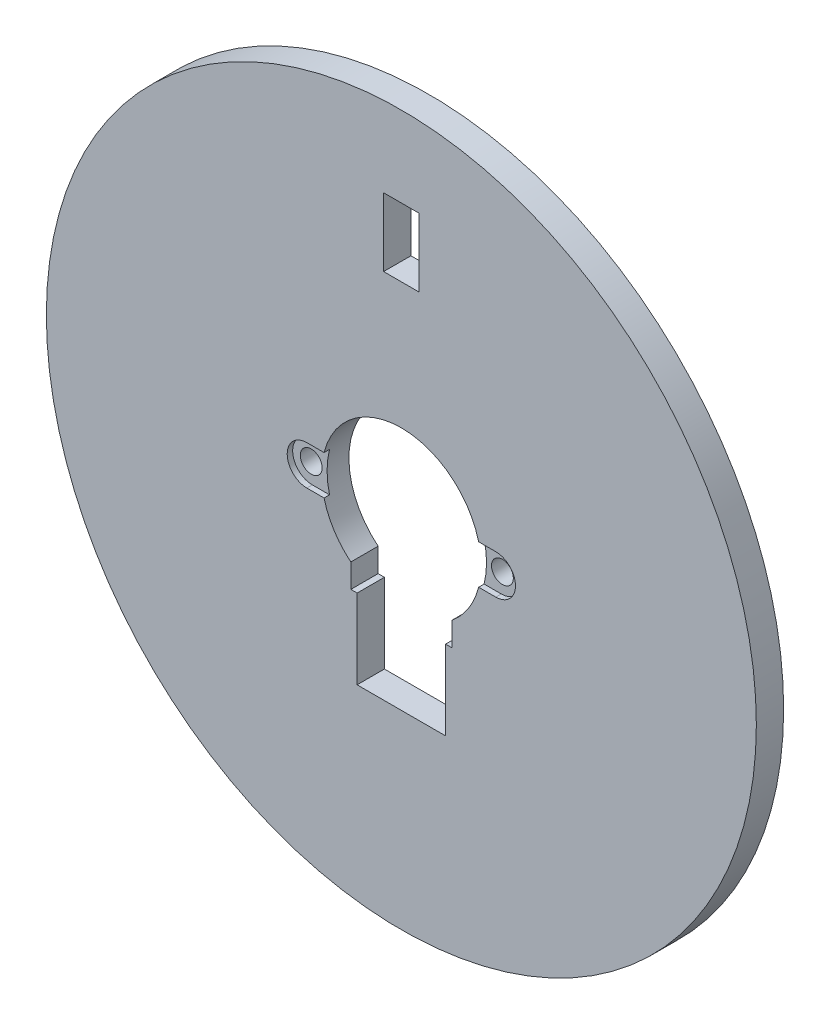
SolidWorks part; units mm, degrees
ref_plane "Front Plane" through (0, 0, 0) normal (0, 0, 1) x (1, 0, 0)
ref_plane "Top Plane" through (0, 0, 0) normal (0, 1, 0) x (1, 0, 0)
ref_plane "Right Plane" through (0, 0, 0) normal (1, 0, 0) x (0, 0, -1)
sketch "Sketch1" plane through (0, 0, 0) normal (0, 0, 1) x (1, 0, 0)
  line L0 (-121.4648, 0) -> (89.658, 0) construction
  line L1 (0, 59.7877) -> (0, -65.1952) construction
  line L2 (-14.1492, 3.6) -> (-17.3, 3.6)
  line L3 (-14.1492, -3.6) -> (-17.3, -3.6)
  line L4 (-9.25, -11.2959) -> (-9.25, -15.647)
  line L5 (14.1492, 3.6) -> (17.3, 3.6)
  line L14 (8.1, -15.647) -> (8.1, -30.2)
  line L15 (14.1492, -3.6) -> (17.3, -3.6)
  line L16 (-8.1, -30.2) -> (8.1, -30.2)
  line L24 (9.25, -11.2959) -> (9.25, -15.647)
  line L25 (8.1, -15.647) -> (9.25, -15.647)
  line L26 (-8.1, -15.647) -> (-9.25, -15.647)
  line L27 (-8.1, -15.647) -> (-8.1, -30.2)
  line L28 (-3.25, 44) -> (3.25, 44) construction
  line L29 (-3.25, 50.25) -> (3.25, 50.25)
  line L30 (-3.25, 50.25) -> (-3.25, 37.75)
  line L31 (-3.25, 37.75) -> (3.25, 37.75)
  line L32 (3.25, 50.25) -> (3.25, 37.75)
  circle A0 centre (0, 0) radius 65
  arc A2 (9.25, -11.2959) -> (-9.25, -11.2959) centre (0, 0) ccw
  arc A3 (17.3, -3.6) -> (17.3, 3.6) centre (17.3, 0) ccw
  arc A4 (-17.3, -3.6) -> (-17.3, 3.6) centre (-17.3, 0) cw
  circle A6 centre (17.5, 0) radius 2
  circle A7 centre (-17.5, 0) radius 2
  circle A8 centre (0, 56) radius 2
  circle A9 centre (0, 32) radius 2
  point P35 (0, -30.2)
  dimension "D2" = 18.5
  dimension "D3" = 14.6
  dimension "D4" = 7.2
  dimension "D8" = 4
  dimension "D5" = 130
  dimension "D13" = 4
  dimension "D6" = 1.15
  dimension "D7" = 0.2
  dimension "D9" = 6.5
  dimension "D10" = 4.3511
  dimension "D11" = 12.5
  dimension "D12" = 44
  dimension "D14" = 30.2
  dimension "D15" = 12
  dimension "D16" = 17.5
extrude "Boss-Extrude1" add sketch "Sketch1" along normal blind 5 contours A0 L3 A4 L2 A2 L5 A3 L15 L24 L25 L14 L16 L27 L26 L4 region at (-63.1615, 0, 0)
extrude "Boss-Extrude2" add sketch "Sketch1<3>" along normal blind 4 contours A4 L3 A2 L2 A7 | L15 A3 L5 A2 A6 region at (-14.6987, 0, 0) region at (15.7246, 3.5013, 0)
sketch "Sketch1<3>" plane through (0, 0, 0) normal (0, 0, 1) x (1, 0, 0) same geometry as "Sketch1"
extrude "Boss-Extrude3" add sketch "Sketch1<4>" along normal blind 1 contours A7 | A6 region at (17.5, 0, 0) region at (-17.5, 0, 0)
sketch "Sketch1<4>" plane through (0, 0, 0) normal (0, 0, 1) x (1, 0, 0) same geometry as "Sketch1"
extrude "Boss-Extrude6" add sketch "Sketch1<6>" along normal blind 5 contours A8 | A9 region at (0, 56, 0) region at (0, 32, 0)
sketch "Sketch1<6>" plane through (0, 0, 0) normal (0, 0, 1) x (1, 0, 0) same geometry as "Sketch1"
extrude "Cut-Extrude1" cut sketch "Sketch1<7>" along normal blind 3 contours A9 | A8 region at (0, 56, 0) region at (0, 32, 0)
sketch "Sketch1<7>" plane through (0, 0, 0) normal (0, 0, 1) x (1, 0, 0) same geometry as "Sketch1"
